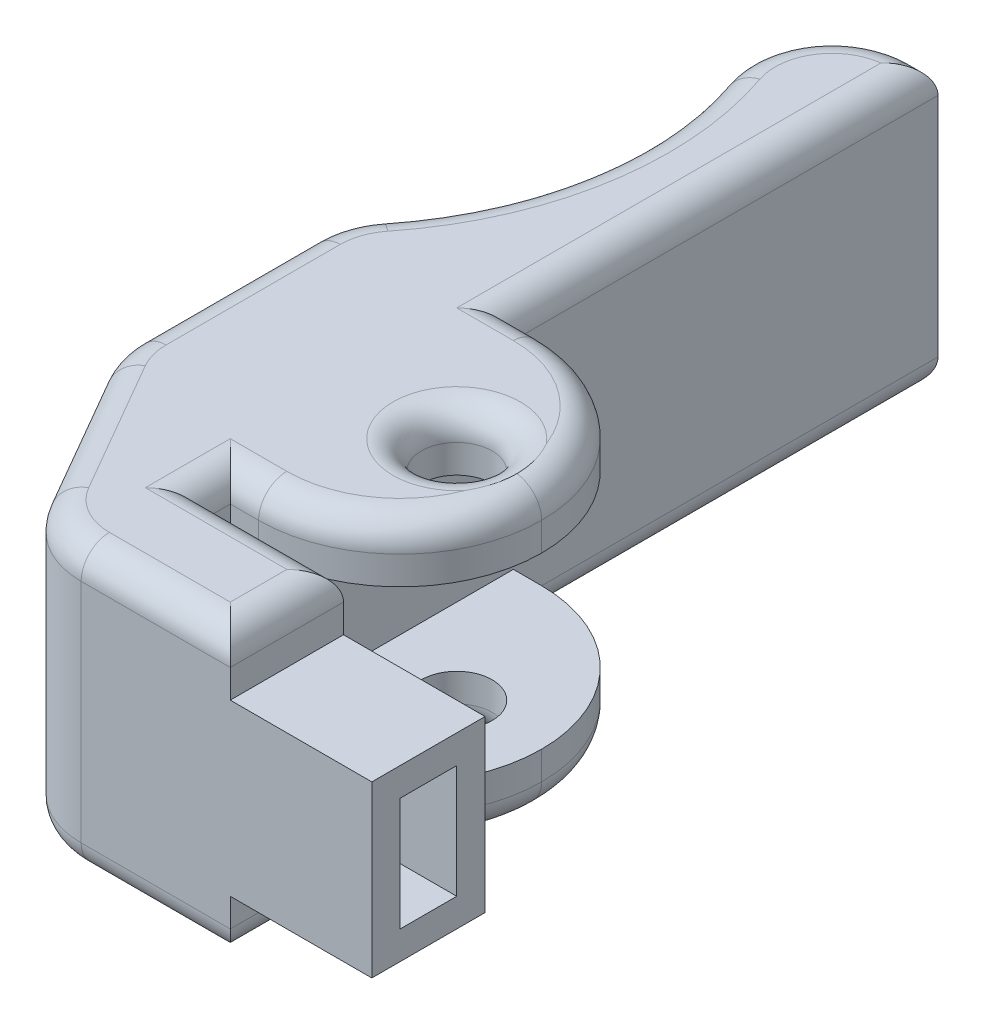
SolidWorks part; units mm, degrees
ref_plane "Alzado" through (0, 0, 0) normal (0, 0, 1) x (1, 0, 0)
ref_plane "Planta" through (0, 0, 0) normal (0, 1, 0) x (1, 0, 0)
ref_plane "Vista lateral" through (0, 0, 0) normal (1, 0, 0) x (0, 0, -1)
sketch "Croquis1" plane through (0, 0, 0) normal (0, 1, 0) x (1, 0, 0)
  line L0 (-9.9046, -8.5) -> (10.6762, -8.5) construction
  line L1 (-3, -5) -> (3, -5)
  line L2 (-3, -5) -> (-3, 5)
  line L3 (-3, 5) -> (3, 5)
  line L4 (3, -5) -> (3, 5)
  line L5 (-3, -5) -> (3, 5) construction
  line L6 (-3, 5) -> (3, -5) construction
  line L7 (7, 2.5928) -> (7, -12.651) construction
  line L8 (7.3581, -6) -> (7, -6)
  line L9 (7, -6) -> (7, -10)
  line L10 (7, -10) -> (-5, -10)
  line L11 (-5, -10) -> (-9, -3.0718)
  line L12 (-9, -3.0718) -> (-9, 20)
  line L13 (-3, -5) -> (-3, -6)
  line L14 (-9, 20) -> (-3, 20)
  line L15 (-3, 20) -> (-3, 5)
  line L16 (-3, -6) -> (7.3581, -6)
  line L17 (-3, 20) -> (-3, 5)
  line L18 (-3, 20) -> (-3, 5)
  line L19 (3, -3.4865) -> (3, -15.8512) construction
  line L20 (-3, -5) -> (-3, -6)
  circle A0 centre (0, 0) radius 1.25
  point P21 (7, -8)
  point P22 (0, 0)
  dimension "D1" = 2.5
  dimension "D2" = 10
  dimension "D3" = 6
  dimension "D4" = 8.5
  dimension "D5" = 4
  dimension "D6" = 16
  dimension "D7" = 15
  dimension "D8" = 4
  dimension "D9" = 60
  dimension "D10" = 12
  dimension "D11" = 10
extrude "Saliente-Extruir1" add sketch "Croquis1" along normal mid plane 10 contours L16 L13 L2 L15 L14 L12 L11 L10 L9 | L1 L4 L3 L2 A0 region at (-2.8834, 0, 0) region at (-4.3357, 0, -3.3305)
fillet "Redondeo1" radius 5 2 edges at (3, 0, 5) (3, 0, -5)
sketch "Croquis2" plane through (7, 0, 0) normal (1, 0, 0) x (0, 0, -1)
  line L0 (3.3526, 0) -> (-16.0457, 0) construction
  line L1 (-10, 3) -> (-6, 3)
  line L2 (-10, -5) -> (-6, -5)
  line L3 (-10, -5) -> (-10, -3)
  line L4 (-10, -5) -> (-6, -5)
  line L5 (-6, -5) -> (-6, 5)
  line L6 (-6, 5) -> (-10, 5)
  line L7 (-10, 5) -> (-10, -5)
  line L8 (-10, -5) -> (-6, -5)
  line L9 (-6, -5) -> (-6, 5)
  line L10 (-6, 5) -> (-10, 5)
  line L11 (-10, 5) -> (-10, -5)
  line L12 (-10, -3) -> (-6, -3)
  line L13 (-6, -5) -> (-6, -3)
  line L14 (-6, 5) -> (-6, 3)
  line L15 (-10, 5) -> (-6, 5)
  line L16 (-10, 5) -> (-10, 3)
  line M13 (-10, -5) -> (-6, -5)
  line M14 (-6, -5) -> (-6, 5)
  line M15 (-6, 5) -> (-10, 5)
  line M16 (-10, 5) -> (-10, -5)
  dimension "D2" = 2
  dimension "D1" = 0
extrude "Cortar-Extruir1" cut sketch "Croquis2" against normal blind 5 contours L1 M16 M14 M15 | L12 M16 M13 M14 region at (7, 4, 8) region at (7, -4, 8)
sketch "Croquis3" plane through (0, 0, 0) normal (1, 0, 0) x (0, 0, -1)
  line L1 (-5, -3) -> (5, -3)
  line L2 (-5, -3) -> (-5, 3)
  line L3 (-5, 3) -> (5, 3)
  line L4 (0, 5) -> (-5, 5)
  line L5 (-5, 5) -> (-5, -5)
  line L6 (-5, -5) -> (0, -5)
  line L7 (0, -5) -> (0, 5)
  line L8 (0, 5) -> (-5, 5)
  line L9 (-5, 5) -> (-5, -5)
  line L10 (-5, -5) -> (0, -5)
  line L11 (0, -5) -> (0, 5)
  line L12 (5, -5) -> (5, 5)
  line L13 (5, 5) -> (0, 5)
  line L14 (0, 5) -> (0, -5)
  line L15 (0, -5) -> (5, -5)
  line L16 (5, -5) -> (5, 5)
  line L17 (5, 5) -> (0, 5)
  line L18 (0, 5) -> (0, -5)
  line L19 (0, -5) -> (5, -5)
  line L20 (5, -3) -> (5, 3)
  line L21 (-5, -3) -> (5, 3) construction
  line L22 (-5, 3) -> (5, -3) construction
  point P6 (0, 0)
  dimension "D3" = 6
  dimension "D1" = 0
  dimension "D2" = 0
extrude "Cortar-Extruir2" cut sketch "Croquis3" against normal up to surface (3 mm away) and the other way blind 5 contours L1 L16 L3 L11 | L1 L11 L3 L2 region at (0, 0, 2.5) region at (0, 0, -2.5) up to face at (-3, 0, 5.5)
sketch "Croquis4" plane through (7, 0, 0) normal (1, 0, 0) x (0, 0, -1)
  line L8 (-7, 2) -> (-9, 2)
  line L9 (-9, 2) -> (-9, -2)
  line L10 (-9, -2) -> (-7, -2)
  line L11 (-7, -2) -> (-7, 2)
  line L12 (-7, 2) -> (-9, 2)
  line L13 (-9, 2) -> (-9, -2)
  line L14 (-9, -2) -> (-7, -2)
  line L15 (-7, -2) -> (-7, 2)
  dimension "D1" = 1
extrude "Cortar-Extruir3" cut sketch "Croquis4" against normal blind 2
sketch "Croquis5" plane through (0, 0, 0) normal (0, 1, 0) x (1, 0, 0)
  line L1 (-9, 20) -> (-6, 20) construction
  line L2 (-9, 20) -> (-9, 5)
  line L3 (-9, 5) -> (-6, 5) construction
  line L4 (-6, 20) -> (-6, 5) construction
  arc A0 (-9, 20) -> (-9, 5) centre (-16.875, 12.5) cw
  dimension "D1" = 15
  dimension "D2" = 3
extrude "Cortar-Extruir4" cut sketch "Croquis5" against normal mid plane 32
fillet "Redondeo2" radius 3 1 edges at (-9, 0, -20)
fillet "Redondeo3" radius 3 3 edges at (-5, 0, 10) (-9, 0, 3.0718) (-9, 0, -5)
fillet "Redondeo4" radius 1 34 edges at (2, -5, 8) (-0.5, -5, 6) (-3, -5, 5.5) (-2.5, -5, 5) (1.5355, -5, 3.5355) (1.5355, -5, -3.5355) (-2.5, -5, -5) (-3, -5, -12.5) (-6.1912, -5, -18.7437) (-6.1565, -5, -10.6614) (-8.8332, -5, -4.8695) (-9, -5, -0.8076) (-8.8978, -5, 3.0444) (-7.2321, -5, 6.134) (-4.7679, -5, 9.5981) (-0.634, -5, 10) (0, -5, 1.25) (0, 5, 1.25) (-8.8978, 5, 3.0444) (-9, 5, -0.8076) (-8.8332, 5, -4.8695) (-6.1565, 5, -10.6614) (-6.1912, 5, -18.7437) (-3, 5, -12.5) (-2.5, 5, -5) (1.5355, 5, -3.5355) (1.5355, 5, 3.5355) (-2.5, 5, 5) (-3, 5, 5.5) (-0.5, 5, 6) (2, 5, 8) (-0.634, 5, 10) (-4.7679, 5, 9.5981) (-7.2321, 5, 6.134)
